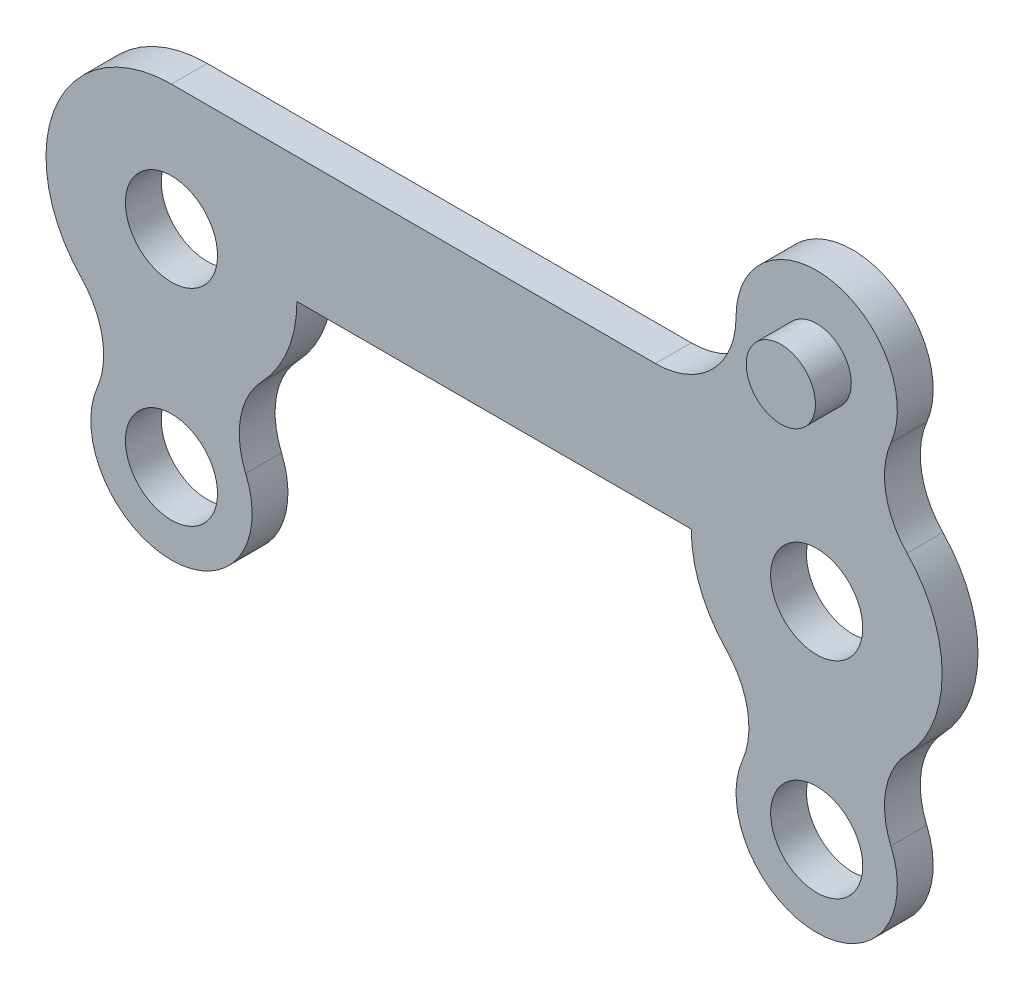
SolidWorks part; units mm, degrees
material "ABS"
ref_plane "Front Plane" through (0, 0, 0) normal (0, 0, 1) x (1, 0, 0)
ref_plane "Top Plane" through (0, 0, 0) normal (0, 1, 0) x (1, 0, 0)
ref_plane "Right Plane" through (0, 0, 0) normal (1, 0, 0) x (0, 0, -1)
sketch "Sketch1" plane through (0, 0, 0) normal (0, 0, 1) x (1, 0, 0)
  line L0 (5.5562, 0) -> (23.0188, 0)
  line L1 (0, 5.5562) -> (28.575, 5.5562)
  line L5 (0, 5.5562) -> (28.575, 5.5562) construction
  circle A0 centre (0, 0) radius 5.5562 construction
  circle A1 centre (28.575, 0) radius 5.5562 construction
  arc A2 (0, 5.5562) -> (0, -5.5562) centre (0, 0) ccw
  arc A3 (28.575, -5.5562) -> (28.575, 5.5562) centre (28.575, 0) ccw
  circle A4 centre (0, 0) radius 1.7859
  circle A5 centre (28.575, 0) radius 1.7859
  arc A6 (0, -5.5562) -> (5.5562, 0) centre (0, 0) ccw
  arc A7 (23.0188, 0) -> (28.575, -5.5562) centre (28.575, 0) ccw
  circle A10 centre (0, -9.1281) radius 3.5719
  circle A12 centre (28.575, -9.1281) radius 1.7859
  circle A15 centre (0, -9.1281) radius 1.7859
  circle A17 centre (28.575, -9.1281) radius 3.5719
  circle A27 centre (-6.5741, -6.3327) radius 3.5719
  circle A28 centre (6.5741, -6.3327) radius 3.5719
  circle A29 centre (22.0009, -6.3327) radius 3.5719
  circle A30 centre (35.1491, -6.3327) radius 3.5719
  circle A31 centre (28.575, 9.1281) radius 1.7859
  circle A32 centre (28.575, 9.1281) radius 3.5719
  circle A33 centre (21.4313, 9.1281) radius 3.5719
  circle A34 centre (35.1491, 6.3327) radius 3.5719
  dimension "D1" = 28.575
  dimension "D2" = 11.1125
  dimension "D3" = 3.5719
  dimension "D6" = 7.1437
  dimension "D7" = 3.5719
sketch "Sketch2" plane through (0, 0, 0) normal (0, 0, 1) x (1, 0, 0)
  line L0 (5.5562, 0) -> (23.0188, 0)
  line L2 (0, 5.5562) -> (28.575, 5.5562)
  circle A0 centre (0, 0) radius 5.5562
  circle A1 centre (28.575, 0) radius 5.5563
  circle A2 centre (28.575, -9.1281) radius 3.5719
  circle A3 centre (0, -9.1281) radius 3.5719
  circle A4 centre (6.5741, -6.3327) radius 3.5719
  circle A5 centre (-6.5741, -6.3327) radius 3.5719
  circle A6 centre (22.0009, -6.3327) radius 3.5719
  circle A7 centre (35.1491, -6.3327) radius 3.5719
  circle A8 centre (28.575, 9.1281) radius 3.5719
  arc A9 (0, -5.5562) -> (5.5562, 0) centre (0, 0) ccw construction
  arc A10 (23.0188, 0) -> (28.575, -5.5562) centre (28.575, 0) ccw construction
  circle A11 centre (28.575, -9.1281) radius 3.5719 construction
  circle A12 centre (0, -9.1281) radius 3.5719 construction
  circle A13 centre (22.0009, -6.3327) radius 3.5719 construction
  circle A15 centre (28.575, 9.1281) radius 3.5719 construction
  circle A16 centre (35.1491, 6.3327) radius 3.5719
  circle A18 centre (35.1491, 6.3327) radius 3.5719 construction
  circle A19 centre (0, 0) radius 2.0399
  circle A20 centre (28.575, 0) radius 2.0399
  circle A21 centre (0, -9.1281) radius 2.0399
  circle A22 centre (28.575, -9.1281) radius 2.0399
  circle A28 centre (28.575, 9.1281) radius 1.5319
  circle A30 centre (21.4313, 9.1281) radius 3.5719
  circle A31 centre (21.4313, 9.1281) radius 3.5719 construction
  dimension "D1" = 4.0799
  dimension "D2" = 4.0799
  dimension "D3" = 3.0639
extrude "Boss-Extrude1" add sketch "Sketch2" along normal blind 1.5875 contours A0 A19 | A5 A3 A0 | A4 A0 A3 | A3 A21 | A2 A22 | A6 A2 A1 | A7 A1 A2 | A1 A20 | A1 L2 A0 L0 | A30 L2 A8 | A16 A8 A1 | A8 A28 region at (14.2875, 2.9628, 0) region at (5.0072, -2.0194, 0) region at (24.7573, 3.8177, 0) region at (2.4105, -5.669, 0) region at (30.9855, 5.669, 0) region at (25.0031, 6.3541, 0) region at (26.1207, 6.6739, 0) region at (26.1645, -5.669, 0) region at (-2.4105, -5.669, 0) region at (1.9148, -6.2332, 0) region at (30.9855, -5.669, 0) region at (30.4898, -6.2332, 0)
extrude "Boss-Extrude3" add sketch "Sketch2<4>" along normal blind 3.175 contours A28 region at (28.575, 9.1281, 0)
sketch "Sketch2<4>" plane through (0, 0, 0) normal (0, 0, 1) x (1, 0, 0) same geometry as "Sketch2"
